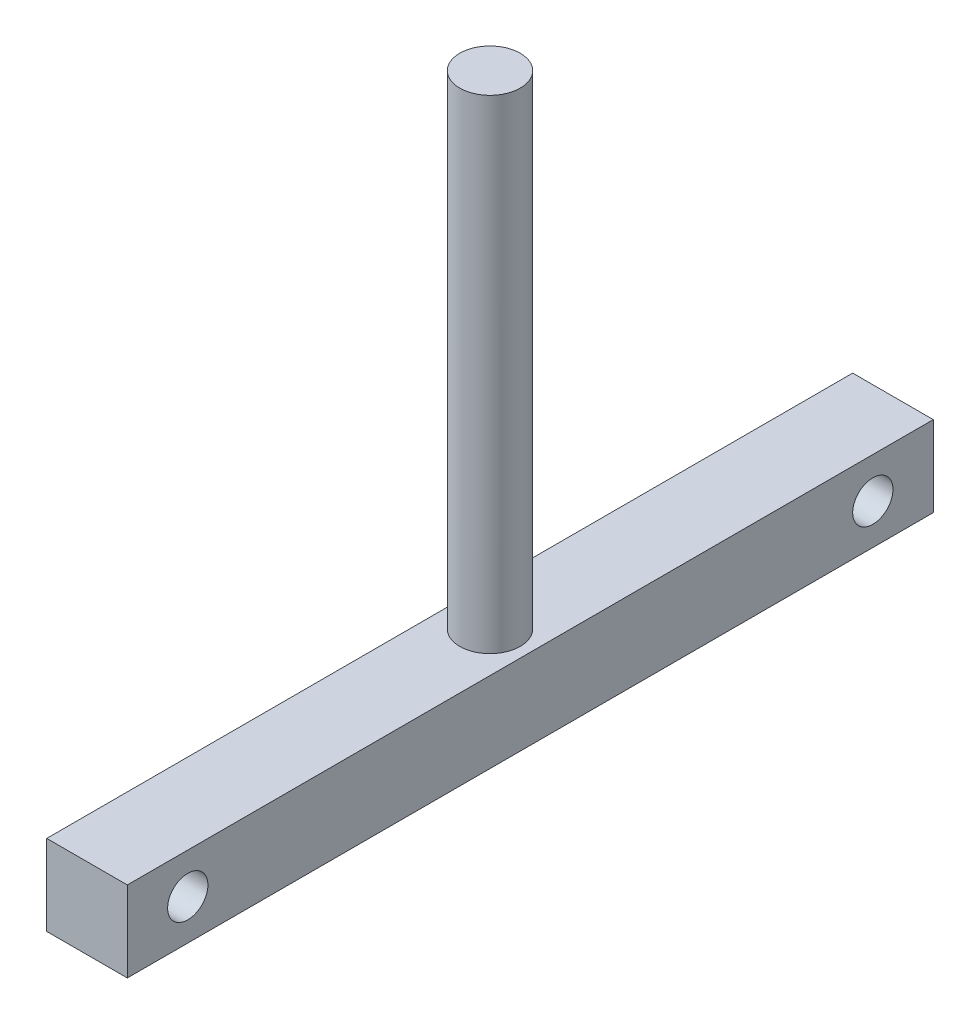
SolidWorks part; units mm, degrees
ref_plane "Front Plane" through (0, 0, 0) normal (0, 0, 1) x (1, 0, 0)
ref_plane "Top Plane" through (0, 0, 0) normal (0, 1, 0) x (1, 0, 0)
ref_plane "Right Plane" through (0, 0, 0) normal (1, 0, 0) x (0, 0, -1)
sketch "Sketch1" plane through (0, 0, 0) normal (0, 0, 1) x (1, 0, 0)
  line L1 (-10, 10) -> (10, 10)
  line L2 (-10, 10) -> (-10, -10)
  line L3 (-10, -10) -> (10, -10)
  line L4 (10, 10) -> (10, -10)
  line L5 (-10, 10) -> (10, -10) construction
  line L6 (-10, -10) -> (10, 10) construction
  circle A0 centre (0, 0) radius 5 construction
  point P1 (0, 0)
  dimension "D3" = 10
  dimension "D1" = 20
  dimension "D2" = 20
extrude "Boss-Extrude1" add sketch "Sketch1" along normal blind 200
sketch "Sketch2" plane through (0, 10, 0) normal (0, 1, 0) x (1, 0, 0)
  line L0 (0, -200) -> (0, 0) construction
  line L1 (10, -200) -> (-10, -200) construction
  line L2 (-10, -100) -> (10, -100) construction
  line L3 (-10, -200) -> (-10, 0) construction
  line L4 (10, -200) -> (10, 0) construction
  circle A0 centre (0, -100) radius 7.5
  dimension "D1" = 15
extrude "Boss-Extrude2" add sketch "Sketch2" along normal blind 120
sketch "Sketch3" plane through (-10, 0, 0) normal (-1, 0, 0) x (0, 0, 1)
  line L0 (0, 0) -> (200, 0) construction
  line L1 (200, 10) -> (200, -10) construction
  line L2 (0, 10) -> (0, -10) construction
  line L3 (100, 10) -> (100, -10) construction
  line L4 (200, 10) -> (0, 10) construction
  line L5 (200, -10) -> (0, -10) construction
  circle A0 centre (15, 0) radius 5
  circle A1 centre (185, 0) radius 5
  dimension "D1" = 10
  dimension "D2" = 15
extrude "Cut-Extrude1" cut sketch "Sketch3" against normal blind 57
